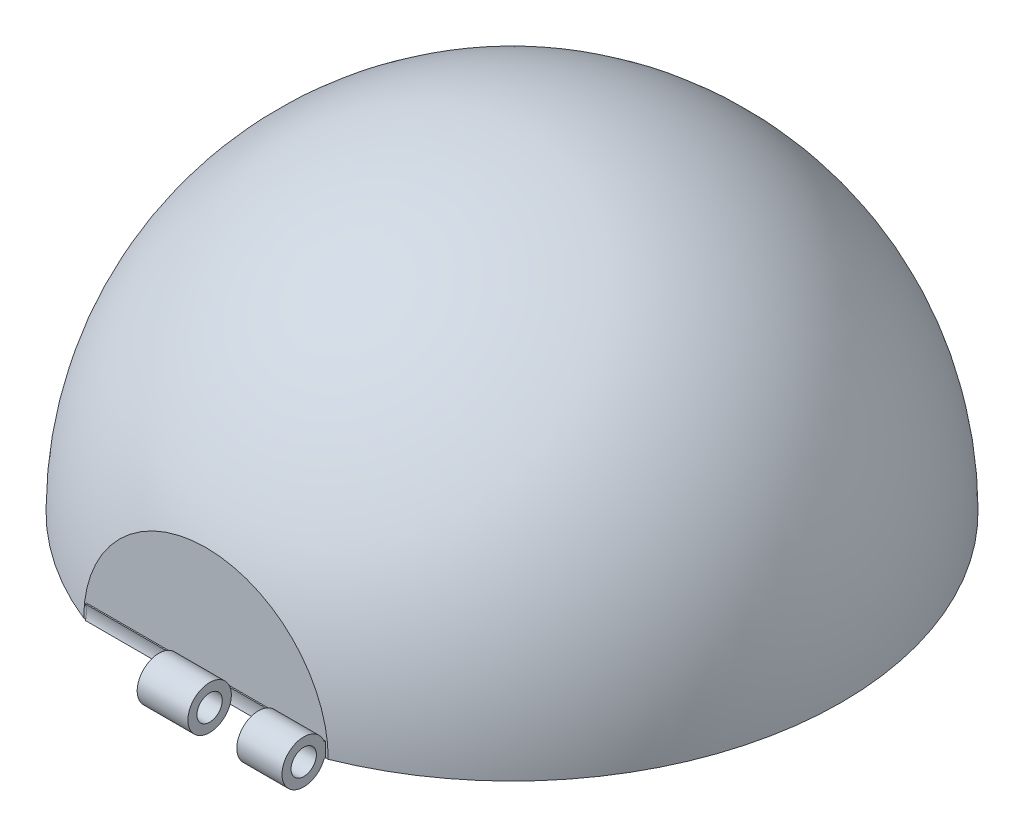
SolidWorks part; units mm, degrees
ref_plane "Front Plane" through (0, 0, 0) normal (0, 0, 1) x (1, 0, 0)
ref_plane "Top Plane" through (0, 0, 0) normal (0, 1, 0) x (1, 0, 0)
ref_plane "Right Plane" through (0, 0, 0) normal (1, 0, 0) x (0, 0, -1)
sketch "Sketch1" plane through (0, 0, 0) normal (0, 0, 1) x (1, 0, 0)
  line L0 (0, 0) -> (45.5, 0)
  line L1 (0, 0) -> (0, 45.5)
  arc A0 (45.5, 0) -> (0, 45.5) centre (0, 0) ccw
  point P1 (0, 45.5)
  dimension "D1" = 45.5
revolve "Revolve1" add sketch "Sketch1" angle 360 about L1
sketch "Sketch2" plane through (0, 0, 0) normal (0, 1, 0) x (1, 0, 0)
  line L1 (-50, 42.2522) -> (50, 42.2522)
  line L2 (-50, 42.2522) -> (-50, 47.2522)
  line L3 (-50, 47.2522) -> (50, 47.2522)
  line L4 (50, 42.2522) -> (50, 47.2522)
  line L5 (-50, -42.2522) -> (50, -42.2522)
  line L6 (-50, -42.2522) -> (-50, -47.2522)
  line L7 (-50, -47.2522) -> (50, -47.2522)
  line L8 (50, -42.2522) -> (50, -47.2522)
  point P8 (0, -42.2522)
  point P10 (0, 42.2522)
  dimension "D1" = 100
  dimension "D2" = 100
  dimension "D3" = 42.2522
  dimension "D4" = 5
  dimension "D5" = 42.2522
  dimension "D6" = 5
extrude "Cut-Extrude1" cut sketch "Sketch2" along normal up to surface up to face at (45.5, 0, 0)
shell "Shell1" thickness 2 removed face at (0, 0, 0)
sketch "Sketch5" plane through (0, 0, 0) normal (1, 0, 0) x (0, 0, -1)
  line L0 (-42.2522, 0) -> (42.2522, 0) construction
  line L1 (-42.2522, 16.8819) -> (-42.2522, 0) construction
  line L2 (-42.2522, 0) -> (-42.4238, 0)
  line L3 (-42.2522, 0) -> (-42.2522, 2)
  line L4 (-42.2522, 2) -> (-42.4238, 2)
  arc A0 (-42.4238, 2) -> (-42.4238, 0) centre (-45.2522, 1) ccw
  circle A1 centre (-45.2522, 1) radius 1.75
  point P17 (0, 0)
  dimension "D1" = 3.5
  dimension "D2" = 6
  dimension "D3" = 1
  dimension "D4" = 2
extrude "Boss-Extrude1" add sketch "Sketch5" along normal up to vertex (16.4927 mm away) and the other way up to vertex (16.4927 mm away) up to point (16.4927, 0, 40.2522) other way up to point (-16.4927, 0, 40.2522)
ref_plane "Plane3" through (3.5, 0, 0) normal (1, 0, 0) x (0, 0, -1)
sketch "Sketch9" plane through (3.5, 0, 0) normal (1, 0, 0) x (0, 0, -1)
  circle A0 centre (-45.2522, 1) radius 3
  arc A1 (-42.4238, 2) -> (-42.4238, 0) centre (-45.2522, 1) ccw construction
extrude "Cut-Extrude10" cut sketch "Sketch9" along normal blind 6.75
ref_plane "Plane4" through (-3.5, 0, 0) normal (1, 0, 0) x (0, 0, -1)
sketch "Sketch10" plane through (-3.5, 0, 0) normal (1, 0, 0) x (0, 0, -1)
  circle A0 centre (-45.2522, 1) radius 3
  arc A1 (-42.4238, 2) -> (-42.4238, 0) centre (-45.2522, 1) ccw construction
extrude "Cut-Extrude11" cut sketch "Sketch10" against normal up to surface (12.9927 mm away) up to face at (-16.4927, 1, 43.5022)
sketch "Sketch11" plane through (0, 0, -42.2522) normal (0, 0, -1) x (-1, 0, 0)
  line L0 (-45.5, 0) -> (-16.8819, 0) construction
  line L1 (-21.8819, 0) -> (14.2501, 0)
  line L2 (-21.8819, 0) -> (-21.8819, 8)
  line L5 (-21.8819, 8) -> (0.1181, 8)
  line L6 (0.1181, 8) -> (0.1181, 5)
  line L7 (0.1181, 5) -> (14.2501, 5)
  line L8 (14.2501, 5) -> (14.2501, 0)
  line L9 (16.8819, 0) -> (-16.8819, 0) construction
  point P1 (0, 0)
  point P3 (13.9636, 0)
  point P13 (9.5243, 0)
  dimension "D1" = 5
  dimension "D2" = 3
  dimension "D3" = 8
  dimension "D4" = 14.132
  dimension "D5" = 22
extrude "Cut-Extrude12" cut sketch "Sketch11" against normal up to body
sketch "Sketch12" plane through (0, 0, 0) normal (0, -1, 0) x (1, 0, 0)
  line L0 (-16.8819, -42.2522) -> (-14.2501, -42.2522) construction
  line L1 (-14.2501, -39.2522) -> (-18.0001, -39.2522)
  line L2 (-14.2501, -39.2522) -> (-14.2501, -42.2522)
  line L3 (-14.2501, -42.2522) -> (-18.0001, -42.2522)
  line L4 (-18.0001, -39.2522) -> (-18.0001, -42.2522)
  line L5 (-14.2501, -40.2522) -> (-14.2501, -42.2522) construction
  point P7 (0, 0)
  point P8 (0, 0)
  point P14 (0, 0)
  dimension "D1" = 3.75
  dimension "D2" = 3
extrude "Cut-Extrude13" cut sketch "Sketch12" against normal blind 4
sketch "Sketch13" plane through (-18.0001, 0, 0) normal (1, 0, 0) x (0, 0, -1)
  line L0 (39.6011, 0) -> (41.7881, 0) construction
  line L1 (39.3986, 4) -> (39.4271, 3.7191)
  line L2 (39.3986, 4) -> (41.5962, 4)
  line L5 (41.5962, 4) -> (41.6098, 3.857)
  arc A0 (39.4271, 3.7191) -> (41.6098, 3.857) centre (40.6946, 1) ccw
  circle A1 centre (40.6946, 1) radius 1.75
  arc A2 (41.7881, 0) -> (41.5962, 4) centre (0, 0) ccw construction
  arc A3 (39.6011, 0) -> (39.3986, 4) centre (0, 0) ccw construction
  point P6 (40.6946, 0)
  point P8 (39.3528, 3.6832)
  dimension "D1" = 3.5
  dimension "D2" = 6
  dimension "D3" = 1
extrude "Boss-Extrude4" add sketch "Sketch13" along normal up to surface (3.75 mm away) up to face at (-14.2501, 4.5, -41.2522)
